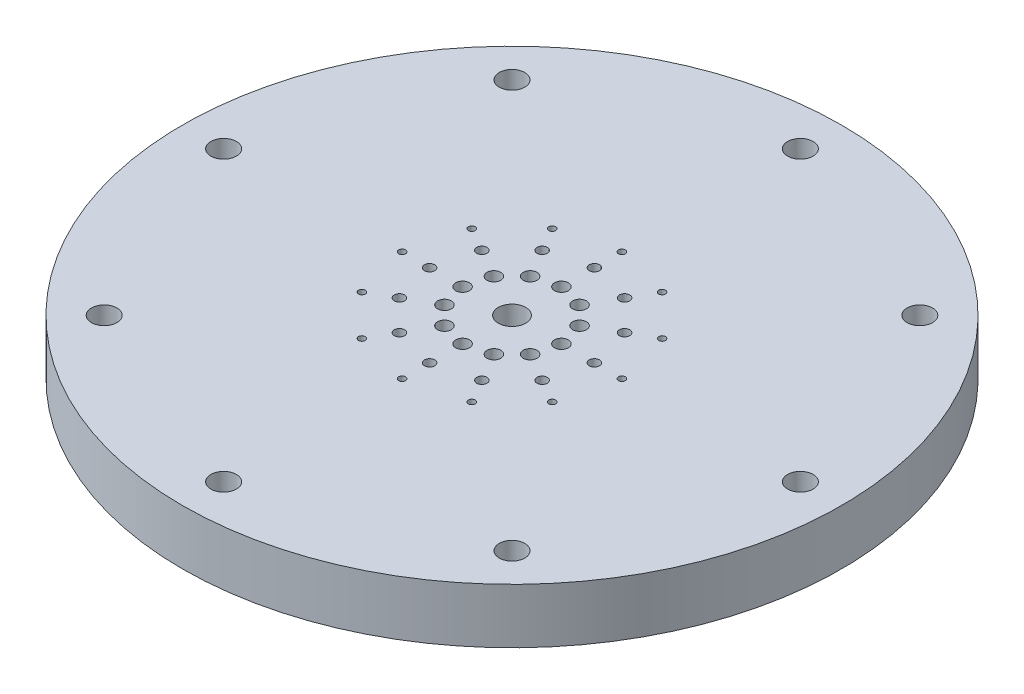
SolidWorks part; units mm, degrees
ref_plane "Front Plane" through (0, 0, 0) normal (0, 0, 1) x (1, 0, 0)
ref_plane "Top Plane" through (0, 0, 0) normal (0, 1, 0) x (1, 0, 0)
ref_plane "Right Plane" through (0, 0, 0) normal (1, 0, 0) x (0, 0, -1)
sketch "Sketch1" plane through (0, 0, 0) normal (0, 1, 0) x (1, 0, 0)
  circle A0 centre (0, 0) radius 38.1
  dimension "D1" = 76.2
extrude "Boss-Extrude1" add sketch "Sketch1" along normal blind 6.35
sketch "Sketch2" plane through (0, 0, 0) normal (0, -1, 0) x (1, 0, 0)
  circle A0 centre (0, 0) radius 33.3375
  circle A1 centre (0, 33.3375) radius 0.762
  dimension "D1" = 66.675
hole_wizard "CBORE for #4 Button Head Cap Screw1" positions "Sketch5" profile "Sketch4" counterbore size "#4" standard "ANSI Inch" end condition through all
sketch "Sketch5" plane through (0, 0, 0) normal (0, -1, 0) x (-1, 0, 0)
  point P0 (0, -33.3375)
sketch "Sketch4" plane through (0, 0, 33.3375) normal (1, 0, 0) x (0, 0, -1)
  line L0 (0, 0) -> (0, 6.35)
  line L1 (0, 6.35) -> (1.4732, 6.35)
  line L3 (1.4732, 6.35) -> (1.4732, 2.8448)
  line L4 (1.4732, 2.8448) -> (2.413, 2.8448)
  line L5 (2.413, 2.8448) -> (2.413, 0)
  line L7 (2.413, 0) -> (0, 0)
  line L11 (0, -6.35) -> (0, 107.95) construction
  dimension "Thru Hole Dia." = 2.9464
  dimension "Thru Hole Depth" = 6.35
  dimension "C'Bore Dia." = 4.826
  dimension "C'Bore Depth" = 2.8448
pattern_circular "CirPattern1" count 8 over 360 about axis through (0, 0, 0) along (0, 1, 0) of "CBORE for #4 Button Head Cap Screw1"
sketch "Sketch6" plane through (0, 6.35, 0) normal (0, 1, 0) x (1, 0, 0)
  circle A0 centre (0, 0) radius 28.575
  dimension "D1" = 57.15
sketch "Sketch7" plane through (0, 0, 0) normal (0, -1, 0) x (1, 0, 0)
  circle A0 centre (0, 12.7) radius 0.3937
  circle A1 centre (0, 9.525) radius 0.5969
  circle A2 centre (0, 5.715) radius 0.8001
  circle A3 centre (0, 0) radius 1.5875
  dimension "D1" = 0.7874
  dimension "D3" = 1.1938
  dimension "D4" = 9.525
  dimension "D5" = 1.6002
  dimension "D6" = 5.715
  dimension "D7" = 3.175
  dimension "D2" = 12.7
extrude "Cut-Extrude1" cut sketch "Sketch7" against normal through all
pattern_circular "CirPattern3" count 12 over 360 about axis through (0, 0, 0) along (0, 1, 0) of "Cut-Extrude1"
